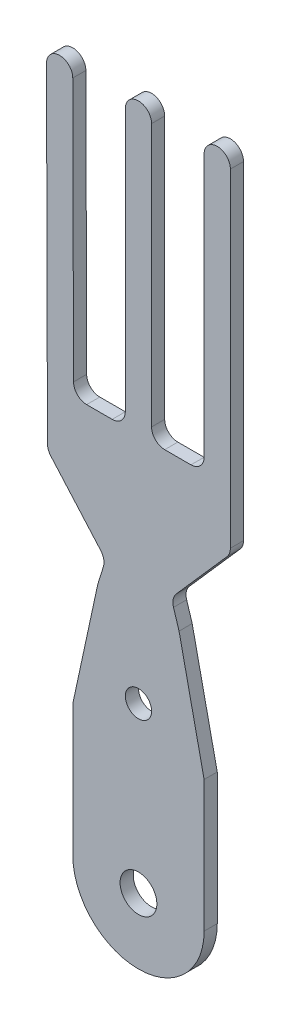
SolidWorks part; units mm, degrees
ref_plane "Alzado" through (0, 0, 0) normal (0, 0, 1) x (1, 0, 0)
ref_plane "Planta" through (0, 0, 0) normal (0, 1, 0) x (1, 0, 0)
ref_plane "Vista lateral" through (0, 0, 0) normal (1, 0, 0) x (0, 0, -1)
sketch "Model" plane through (0, 0, 0) normal (0, 0, 1) x (1, 0, 0)
  line L0 (50.2074, -7.3917) -> (48.2987, 1.4364)
  line L1 (40.2074, -7.3931) -> (42.112, 1.4366)
  line L4 (42.112, 1.4366) -> (42.535, 2.7925)
  line L5 (42.3245, 3.7835) -> (38.5336, 8.0978)
  line L6 (38.206, 33.8533) -> (38.2788, 8.8549)
  line L7 (47.206, 12.8533) -> (49.206, 12.8533)
  line L9 (40.2643, 13.8503) -> (40.206, 33.8591)
  line L10 (38.206, 33.8533) -> (52.206, 33.8533) construction
  line L11 (50.206, 33.8533) -> (50.206, 13.8517)
  line L12 (50.2088, -17.3931) -> (40.2088, -17.3931) construction
  line L13 (50.2074, -7.3917) -> (50.2088, -17.3931)
  line L14 (51.9481, 8.1715) -> (48.0874, 3.7835)
  line L15 (45.206, -23.2096) -> (45.206, 1.7904) construction
  line L16 (47.706, 10.4884) -> (55.206, 10.4884) construction
  line L17 (47.8764, 2.7925) -> (48.2987, 1.4364)
  line L19 (42.3245, 3.7835) -> (48.0874, 3.7835) construction
  line L20 (47.8764, 2.7925) -> (42.535, 2.7925) construction
  line L21 (52.206, 33.8533) -> (52.206, 8.8549)
  line L22 (44.206, 33.8533) -> (44.206, 13.8533)
  line L24 (46.206, 33.8533) -> (46.206, 13.8517)
  line L25 (41.2617, 12.8533) -> (43.206, 12.8533)
  line L26 (38.206, 33.8533) -> (44.206, 33.8533) construction
  line L27 (39.2031, 34.8533) -> (51.206, 34.8533) construction
  line L28 (38.2788, 8.8549) -> (52.206, 8.8549) construction
  line L29 (40.2074, -7.3931) -> (40.2088, -17.3931)
  arc A0 (48.0874, 3.7835) -> (47.8764, 2.7925) centre (48.8642, 3.1001) ccw
  arc A4 (42.535, 2.7925) -> (42.3245, 3.7835) centre (41.5473, 3.1006) ccw
  arc A7 (38.2788, 8.8549) -> (38.5336, 8.0978) centre (39.3108, 8.7807) ccw
  arc A8 (51.9481, 8.1715) -> (52.206, 8.8549) centre (51.1714, 8.8549) ccw
  arc A9 (40.206, 33.8591) -> (38.206, 33.8533) centre (39.206, 33.8533) ccw
  arc A10 (41.2617, 12.8533) -> (40.2643, 13.8503) centre (41.2643, 13.8533) cw
  arc A11 (52.206, 33.8533) -> (50.206, 33.8533) centre (51.206, 33.8533) ccw
  arc A12 (46.206, 33.8533) -> (44.206, 33.8533) centre (45.206, 33.8533) ccw
  arc A13 (40.2088, -17.3931) -> (50.2088, -17.3931) centre (45.2088, -17.3931) ccw
  arc A14 (47.206, 12.8533) -> (46.206, 13.8517) centre (47.206, 13.8533) cw
  arc A15 (50.206, 13.8517) -> (49.206, 12.8533) centre (49.206, 13.8533) cw
  circle A16 centre (45.2088, -17.3931) radius 1.4
  arc A17 (44.206, 13.8533) -> (43.206, 12.8533) centre (43.206, 13.8533) cw
  circle A18 centre (45.2088, -4.8931) radius 1
  point P0 (0, 0)
  dimension "D2" = 2
  dimension "D4" = 12.5
  dimension "D5" = 2
  dimension "D6" = 2
  dimension "D7" = 21
  dimension "D8" = 4
  dimension "D11" = 10
  dimension "D9" = 10
  dimension "D14" = 1
  dimension "D16" = 20
base flange "Brida base1" sketch "Model" thickness 1 reverse thickness direction no parameters "D1"=0.7366
sketch "Líneas de pliegue1" [suppressed] plane through (0, 0, 0) normal (0, 1, 0) x (1, 0, 0)
sketch "Cuadro delimitador1" [suppressed] plane through (0, 0, 0) normal (0, 1, 0) x (1, 0, 0)
sheet metal parameters "Chapa metálica1" thickness 1 parameters "D1"=0.7366
flat pattern "Chapa desplegada1" [suppressed]
sketch "Líneas de pliegue2" plane through (0, 0, 0) normal (0, 0, 1) x (1, 0, 0)
sketch3d "Cuadro delimitador2" [suppressed]
  line L0 (1, 0.9996, 0) -> (1, -56.2461, 0) construction
  line L1 (-13, 0.9996, 0) -> (-13, -56.2461, 0) construction
  line L2 (1, 0.9996, 0) -> (-13, 0.9996, 0) construction
  line L3 (1, -56.2461, 0) -> (-13, -56.2461, 0) construction
